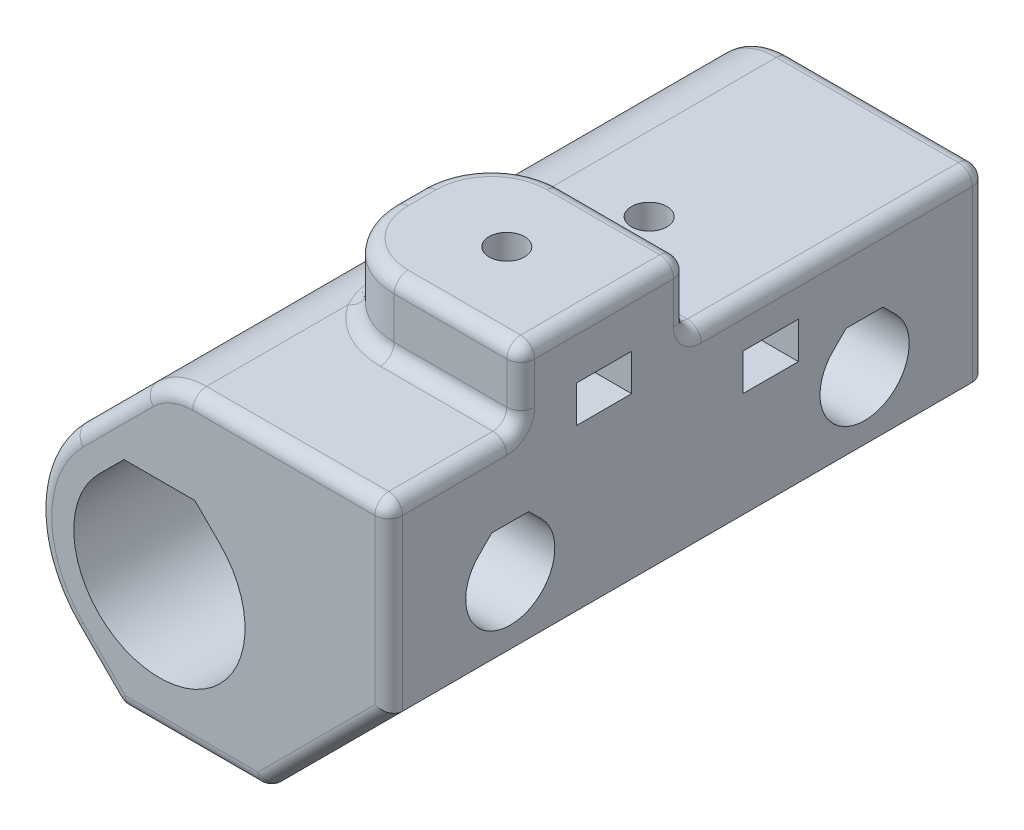
SolidWorks part; units mm, degrees
ref_plane "Front Plane" through (0, 0, 0) normal (0, 0, 1) x (1, 0, 0)
ref_plane "Top Plane" through (0, 0, 0) normal (0, 1, 0) x (1, 0, 0)
ref_plane "Right Plane" through (0, 0, 0) normal (1, 0, 0) x (0, 0, -1)
sketch "Sketch1" plane through (0, 0, 0) normal (0, 0, 1) x (1, 0, 0)
  line L0 (-12.3744, -12.3744) -> (-5.7487, -19)
  line L1 (-12.3744, 12.3744) -> (-2.2777, 22.4711)
  line L2 (4.7934, 25.4) -> (33, 25.4)
  line L3 (33, 25.4) -> (33, -1)
  line L4 (15, -19) -> (-5.7487, -19)
  line L5 (15, -19) -> (33, -1)
  line L6 (8.7151, 8.7151) -> (5.1052, 12.325)
  line L7 (5.1052, 12.325) -> (-5.1052, 12.325)
  line L8 (-5.1052, 12.325) -> (-8.7151, 8.7151)
  arc A0 (-8.7151, 8.7151) -> (8.7151, 8.7151) centre (0, 0) ccw
  arc A1 (4.7934, 25.4) -> (-2.2777, 22.4711) centre (4.7934, 15.4) ccw
  arc A2 (-12.3744, 12.3744) -> (-12.3744, -12.3744) centre (0, 0) ccw
  dimension "D2" = 135
  dimension "D4" = 19
  dimension "D3" = 90
  dimension "D5" = 135
  dimension "D11" = 15
  dimension "D16" = 17.5
  dimension "D14" = 33
  dimension "D6" = 24.65
  dimension "D10" = 10
  dimension "D7" = 25.4
  dimension "D8" = 135
  dimension "D9" = 135
extrude "Boss-Extrude1" add sketch "Sketch1" along normal mid plane 86
sketch "Sketch10" plane through (33, 0, 0) normal (1, 0, 0) x (0, 0, -1)
  line L0 (-43, 25.4) -> (43, 25.4) construction
  line L2 (0, 25.4) -> (0, -19) construction
  line L3 (-43, -19) -> (43, -19) construction
  line L4 (-30.035, 12.935) -> (-28.1566, 14.8135)
  line L5 (-28.1566, 14.8135) -> (-22.8434, 14.8135)
  line L6 (-22.8434, 14.8135) -> (-20.965, 12.935)
  line L7 (22.8434, 14.8135) -> (20.965, 12.935)
  line L8 (28.1566, 14.8135) -> (22.8434, 14.8135)
  line L9 (30.035, 12.935) -> (28.1566, 14.8135)
  arc A0 (-30.035, 12.935) -> (-20.965, 12.935) centre (-25.5, 8.4) ccw
  arc A1 (30.035, 12.935) -> (20.965, 12.935) centre (25.5, 8.4) cw
  dimension "D1" = 12.827
  dimension "D2" = 17
  dimension "D3" = 25.5
  dimension "D4" = 135
  dimension "D5" = 135
ref_axis "Axis1" through (0, 0, 43) along (0, 0, -1)
ref_plane "Plane1" through (0, 0, 0) normal (1, 0, 0) x (0, 0, -1)
ref_plane "Plane2" through (15.25, 0, 0) normal (1, 0, 0) x (0, 0, -1)
extrude "Cut-Extrude9" cut sketch "Sketch10" against normal up to surface (17.75 mm away) up to plane "Plane2"
sketch "Sketch11" plane through (0, 25.4, 0) normal (0, 1, 0) x (1, 0, 0)
  line L0 (33, 0) -> (-17.5, 0) construction
  line L1 (33, -43) -> (33, 43) construction
  line L2 (-17.5, 43) -> (-17.5, -43) construction
  line L5 (0, -43) -> (0, 43) construction
  circle A0 centre (15.5, 12) radius 2.55
  circle A1 centre (15.5, 12) radius 11 construction
  dimension "D1" = 15.5
  dimension "D2" = 22
  dimension "D3" = 12
  dimension "D4" = 5.1
extrude "Cut-Extrude10" cut sketch "Sketch11" against normal blind 15
sketch "Sketch12" plane through (0, 25.4, 0) normal (0, 1, 0) x (1, 0, 0)
  line L0 (14.7934, 0) -> (33, 0)
  line L2 (33, -43) -> (33, 43) construction
  line L3 (33, 0) -> (33, -24)
  line L4 (14.7934, -24) -> (33, -24)
  line L5 (4.7934, -43) -> (4.7934, 43) construction
  line L6 (4.7934, -14) -> (4.7934, -10)
  arc A0 (14.7934, -24) -> (4.7934, -14) centre (14.7934, -14) cw
  arc A1 (4.7934, -10) -> (14.7934, 0) centre (14.7934, -10) cw
  dimension "D2" = 10
  dimension "D1" = 24
extrude "Boss-Extrude2" add sketch "Sketch12" along normal blind 10
sketch "Sketch13" plane through (0, 35.4, 0) normal (0, 1, 0) x (1, 0, 0)
  line L0 (33, 0) -> (14.7934, 0) construction
  line L3 (0, -43) -> (0, 43) construction
  circle A0 centre (19, -12) radius 2.55
  dimension "D1" = 5.1
  dimension "D2" = 12
  dimension "D3" = 19
extrude "Cut-Extrude11" cut sketch "Sketch13" against normal blind 19
ref_plane "Plane3" through (0, 27.4, 0) normal (0, 1, 0) x (1, 0, 0)
sketch "Sketch14" plane through (0, 27.4, 0) normal (0, 1, 0) x (1, 0, 0)
  line L0 (19, -12) -> (33, -12) construction
  line L1 (33, -24) -> (33, 0) construction
  line L2 (33, -15.975) -> (33, -8.025)
  line L3 (14.4101, -12) -> (16.705, -15.975)
  line L4 (16.705, -15.975) -> (33, -15.975)
  line L7 (33, -8.025) -> (16.705, -8.025)
  line L8 (16.705, -8.025) -> (14.4101, -12)
  line L9 (23.2868, -12.525) -> (24.456, -10.5) [skipped]
  line L10 (23.2868, -11.475) -> (22.1177, -9.45) [skipped]
  circle A0 centre (19, -12) radius 3.975 construction
  dimension "D1" = 7.95
extrude "Cut-Extrude12" cut sketch "Sketch14" against normal blind 5.3
ref_plane "Plane4" through (0, 19.4, 0) normal (0, 1, 0) x (1, 0, 0)
sketch "Sketch15" plane through (0, 19.4, 0) normal (0, 1, 0) x (1, 0, 0)
  line L1 (10.9101, 12) -> (13.205, 8.025)
  line L2 (13.205, 8.025) -> (33, 8.025)
  line L3 (33, 8.025) -> (33, 15.975)
  line L4 (33, 15.975) -> (33.0043, 15.9616)
  line L5 (33, 15.975) -> (13.205, 15.975)
  line L6 (13.205, 15.975) -> (10.9101, 12)
  line L7 (10.7084, 12) -> (33, 12) construction
  line L8 (33, 0) -> (33, 43) construction
  line L10 (20.1792, 11.8454) -> (17.841, 15.8953) [skipped]
  line L11 (17.7057, 7.8704) -> (20.0439, 11.9203) [skipped]
  circle A0 centre (15.5, 12) radius 3.975 construction
  dimension "D1" = 7.95
extrude "Cut-Extrude13" cut sketch "Sketch15" against normal blind 5.3 contours L5 L6 L1 L2 L3 region at (22.5183, 19.4, -12)
sketch "Sketch16" plane through (0, 19.4, 0) normal (0, -1, 0) x (1, 0, 0)
  circle A0 centre (15.5, -12) radius 2.55 construction
  circle A1 centre (15.5, -12) radius 2.55
extrude "Boss-Extrude3" add sketch "Sketch16" against normal blind 0.22
sketch "Sketch17" plane through (0, 27.4, 0) normal (0, -1, 0) x (1, 0, 0)
  line L5 (14.4101, 12) -> (16.705, 8.025)
  line L6 (16.705, 8.025) -> (33, 8.025)
  line L7 (33, 8.025) -> (33, 15.975)
  line L8 (33, 15.975) -> (16.705, 15.975)
  line L9 (16.705, 15.975) -> (14.4101, 12)
  line L10 (14.4101, 12) -> (16.705, 8.025)
  line L11 (16.705, 8.025) -> (33, 8.025)
  line L12 (33, 8.025) -> (33, 15.975)
  line L13 (33, 15.975) -> (16.705, 15.975)
  line L14 (16.705, 15.975) -> (14.4101, 12)
  dimension "D1" = 0
extrude "Boss-Extrude4" add sketch "Sketch17" against normal blind 0.22
fillet "Fillet10" radius 2 33 edges at (33, 25.4, -21.5) (-9.0616, -15.6872, 43) (-17.5, 0, 43) (-9.0616, -15.6872, -43) (-17.5, 0, -43) (33, 30.4, 0) (33, 35.4, 12) (23.8967, 35.4, 0) (-7.326, 17.4227, 43) (33, 12.2, 43) (24, -10, 43) (24, -10, -43) (33, 12.2, -43) (18.8967, 25.4, -43) (-7.326, 17.4227, -43) (23.8967, 35.4, 24) (7.7223, 35.4, 21.0711) (4.7934, 35.4, 12) (7.7223, 35.4, 2.9289) (18.8967, 25.4, 43) (0.9666, 24.6388, 43) (0.9666, 24.6388, -43) (33, 30.4, 24) (23.8967, 25.4, 0) (7.7223, 25.4, 2.9289) (4.7934, 25.4, 12) (23.8967, 25.4, 24) (15, -19, 0) (-5.7487, -19, 0) (4.6256, -19, -43) (4.6256, -19, 43) (33, 25.4, 33.5) (7.7223, 25.4, 21.0711)
